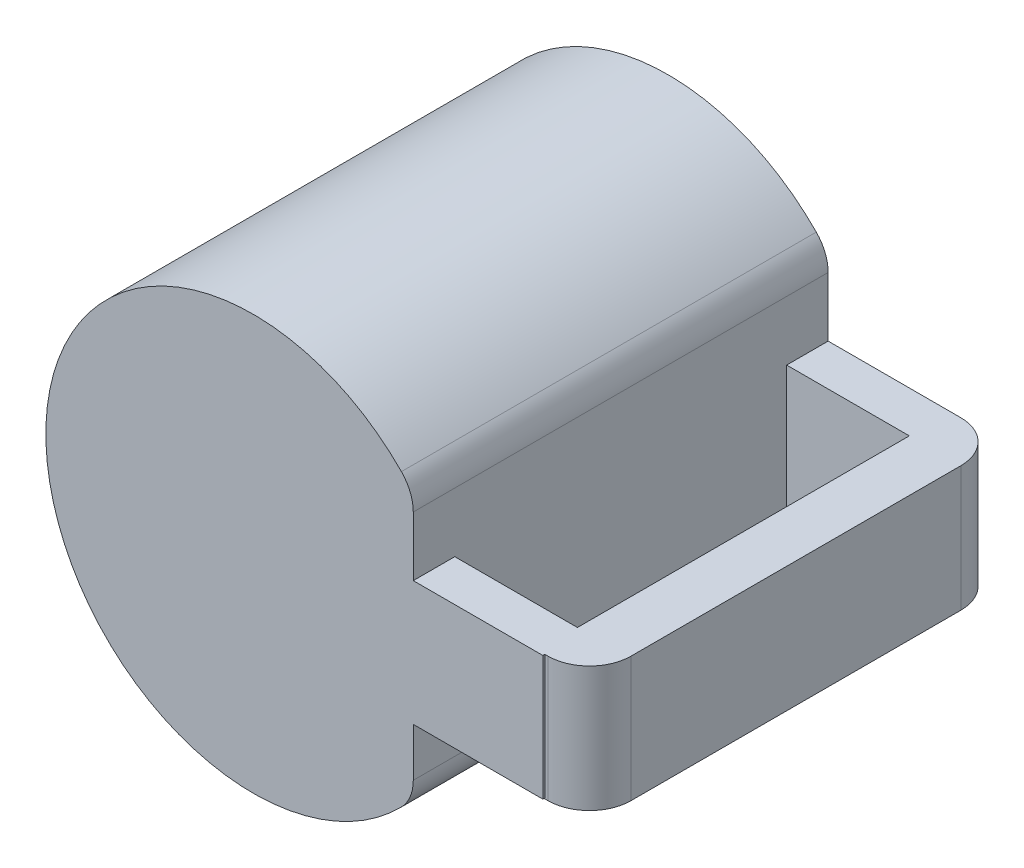
SolidWorks part; units mm, degrees
ref_plane "前基準面" through (0, 0, 0) normal (0, 0, 1) x (1, 0, 0)
ref_plane "上基準面" through (0, 0, 0) normal (0, 1, 0) x (1, 0, 0)
ref_plane "右基準面" through (0, 0, 0) normal (1, 0, 0) x (0, 0, -1)
sketch "草圖1" plane through (0.3827, 0, 0) normal (0, 0, 1) x (1, 0, 0)
  circle A0 centre (-75.5944, 2.55) radius 5
extrude "填料-伸長1" add sketch "草圖1" along normal blind 10 contours A0
ref_plane "平面1" through (0, 0, 9) normal (0, 0, 1) x (1, 0, 0)
sketch "草圖9" plane through (6.1278, 0, 9) normal (0, 0, 1) x (1, 0, 0)
  line L0 (-79.2052, 4.535) -> (-72.0845, 4.535)
  line L1 (-72.0845, 4.535) -> (-72.0845, 0)
  line L2 (-72.0845, 0) -> (-79.2052, 0)
  line L3 (-79.2052, 0) -> (-79.2052, 4.535)
extrude "填料-伸長6" add sketch "草圖9" along normal blind 1
sketch "草圖11" plane through (9.5745, 4.535, 0.4843) normal (0, 1, 0) x (1, 0, 0)
  line L0 (-75.5559, -9) -> (-75.5559, 0)
  line L2 (-75.5559, 0) -> (-76.8136, 0)
  line L3 (-76.8136, 0) -> (-76.8136, -9)
  line L4 (-76.8136, -9) -> (-75.5559, -9)
extrude "填料-伸長7" add sketch "草圖11" against normal blind 4.5 separate body
sketch "草圖12" plane through (-67.2391, 0, 0) normal (-1, 0, 0) x (0, 0, 1)
  line L0 (0.4843, 4.535) -> (0.4843, 0)
  line L1 (0.4843, 4.535) -> (1.4836, 4.535)
  line L2 (1.4836, 4.535) -> (1.4836, 0.035)
  line L3 (0.4843, 0.035) -> (9.4843, 0.035) construction
  line L4 (1.4836, 0.035) -> (0.4843, 0)
extrude "填料-伸長8" add sketch "草圖12" along normal blind 6
fillet "圓角8" radius 1 1 edges at (-65.9814, 2.285, 0.4843)
fillet "圓角9" radius 1 1 edges at (-65.9567, 2.2675, 10)
sketch "草圖13" plane through (0, 0, 0) normal (0, 0, -1) x (-1, 0, 0)
  line L0 (71.3554, 5.7325) -> (71.3554, -0.6325)
  circle A0 centre (75.2117, 2.55) radius 5 construction
  arc A1 (71.3554, 5.7325) -> (71.3554, -0.6325) centre (75.2117, 2.55) ccw
extrude "除料-伸長1" cut sketch "草圖13" against normal blind 10
sketch "草圖14" plane through (-71.3554, 0, 0) normal (1, 0, 0) x (0, 0, -1)
  line L0 (-10, -0.6325) -> (-10, 5.7325) construction
  line L1 (-10, 3.9175) -> (-9, 3.9175)
  line L2 (-10, 3.9175) -> (-10, 0.9175)
  line L3 (-10, 0.9175) -> (-9, 0.9175)
  line L4 (-9, 3.9175) -> (-9, 0.9175)
sketch "草圖15" plane through (-71.3554, 0, 0) normal (1, 0, 0) x (0, 0, -1)
  line L0 (0, -0.6325) -> (0, 5.7325) construction
  line L1 (0, 3.9175) -> (-1, 3.9175)
  line L2 (0, 3.9175) -> (0, 0.9175)
  line L3 (0, 0.9175) -> (-1, 0.9175)
  line L4 (-1, 3.9175) -> (-1, 0.9175)
extrude "填料-伸長9" add sketch "草圖14" along normal blind 3.122 contours L4 L3 L2 L1
extrude "填料-伸長10" add sketch "草圖15" along normal blind 4
sketch "草圖16" plane through (-67.3554, 0, 0) normal (1, 0, 0) x (0, 0, -1)
  line L1 (0, 3.9175) -> (-9.9523, 3.9175)
  line L2 (0, 3.9175) -> (0, 0.9)
  line L3 (0, 0.9) -> (-9.9523, 0.9)
  line L4 (-9.9523, 3.9175) -> (-9.9523, 0.9)
extrude "填料-伸長11" add sketch "草圖16" along normal blind 0.2 and the other way blind 1.0436
fillet "圓角11" radius 1 1 edges at (-67.1554, 2.4088, 0)
fillet "圓角12" radius 1 1 edges at (-67.1554, 2.4088, 9.9523)
fillet "圓角13" radius 1 1 edges at (-71.3554, 5.7325, 5)
fillet "圓角14" radius 1 1 edges at (-71.3554, -0.6325, 5)
